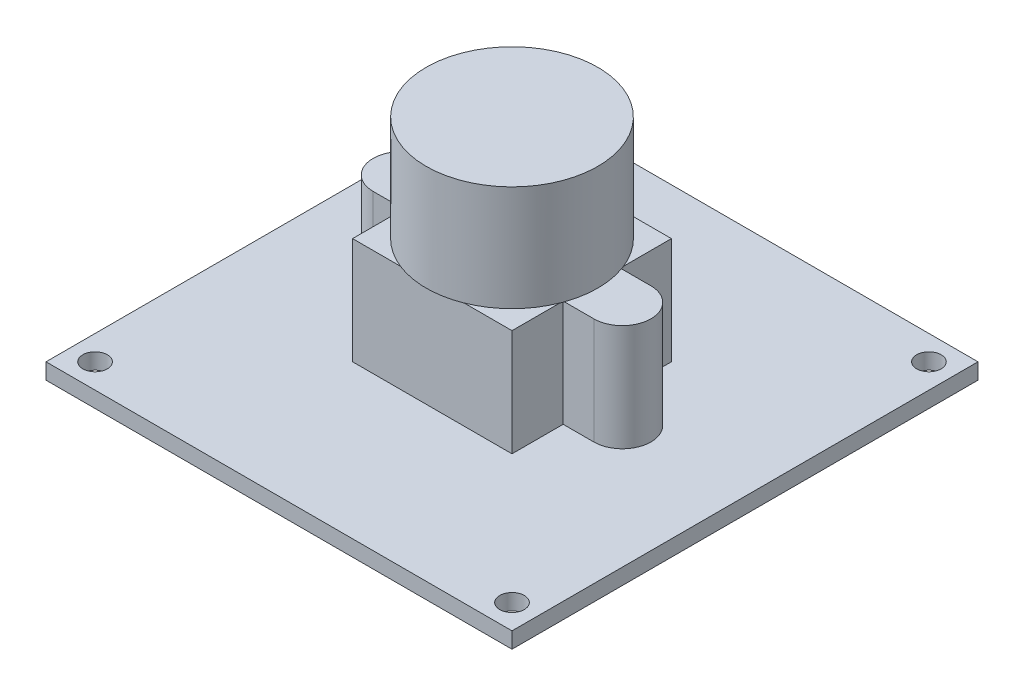
SolidWorks part; units mm, degrees
ref_plane "前视基准面" through (0, 0, 0) normal (0, 0, 1) x (1, 0, 0)
ref_plane "上视基准面" through (0, 0, 0) normal (0, 1, 0) x (1, 0, 0)
ref_plane "右视基准面" through (0, 0, 0) normal (1, 0, 0) x (0, 0, -1)
sketch "Sketch1" plane through (0, 0, 0) normal (0, 1, 0) x (1, 0, 0)
  line L0 (4.6135, 13.9942) -> (4.6135, 34.0904) construction
  line L5 (-14.3865, 13.9942) -> (23.6135, 13.9942)
  line L6 (-14.3865, 13.9942) -> (-14.3865, -24.0058)
  line L7 (-14.3865, -24.0058) -> (23.6135, -24.0058)
  line L8 (23.6135, 13.9942) -> (23.6135, -24.0058)
  line L9 (-14.3865, -5.0058) -> (-25.275, -5.0058) construction
  line L11 (-12.3865, -22.0058) -> (21.6135, -22.0058) construction
  line L12 (-12.3865, -22.0058) -> (-12.3865, 11.9942) construction
  line L13 (-12.3865, 11.9942) -> (21.6135, 11.9942) construction
  line L14 (21.6135, -22.0058) -> (21.6135, 11.9942) construction
  line L15 (-12.3865, -22.0058) -> (21.6135, 11.9942) construction
  line L16 (-12.3865, 11.9942) -> (21.6135, -22.0058) construction
  circle A0 centre (-12.3865, 11.9942) radius 1
  circle A1 centre (21.6135, 11.9942) radius 1
  circle A2 centre (21.6135, -22.0058) radius 1
  circle A3 centre (-12.3865, -22.0058) radius 1
  point P5 (4.6135, -5.0058)
  point P13 (4.6135, 13.9942)
  dimension "D1" = 38
  dimension "D2" = 38
  dimension "D3" = 34
  dimension "D4" = 34
extrude "Boss-Extrude1" add sketch "Sketch1" along normal blind 1.3
sketch "Sketch2" plane through (0, 1.3, 0) normal (0, 1, 0) x (1, 0, 0)
  line L0 (4.6135, 13.9942) -> (4.6135, -32.1036) construction
  line L2 (-14.3865, -5.0058) -> (-25.698, -5.0058) construction
  line L4 (-4.3865, -5.0058) -> (13.6135, -5.0058) construction
  line L5 (-1.8865, -11.5058) -> (11.1135, -11.5058)
  line L6 (-1.8865, -11.5058) -> (-1.8865, -7.3337)
  line L7 (-1.8865, 1.4942) -> (11.1135, 1.4942)
  line L8 (11.1135, -11.5058) -> (11.1135, -7.3337)
  line L9 (-1.8865, -11.5058) -> (11.1135, 1.4942) construction
  line L10 (-1.8865, 1.4942) -> (11.1135, -11.5058) construction
  line L11 (-4.3865, -2.6778) -> (-1.8865, -2.6778)
  line L12 (-4.3865, -7.3337) -> (-1.8865, -7.3337)
  line L13 (11.1135, -2.6778) -> (11.1135, 1.4942)
  line L14 (-1.8865, -2.6778) -> (-1.8865, 1.4942)
  line L15 (11.1135, -2.6778) -> (13.6135, -2.6778)
  line L16 (11.1135, -7.3337) -> (13.6135, -7.3337)
  arc A0 (-4.3865, -2.6778) -> (-4.3865, -7.3337) centre (-4.3865, -5.0058) ccw
  arc A1 (13.6135, -7.3337) -> (13.6135, -2.6778) centre (13.6135, -5.0058) ccw
  point P1 (4.6135, -5.0058)
  point P9 (4.6135, -5.0058)
  dimension "D1" = 13
  dimension "D2" = 13
  dimension "D3" = 18
extrude "Boss-Extrude2" add sketch "Sketch2" along normal blind 8.7
sketch "Sketch3" plane through (0, 10, 0) normal (0, 1, 0) x (1, 0, 0)
  circle A0 centre (4.6135, -5.0058) radius 7
extrude "Boss-Extrude3" add sketch "Sketch3" along normal blind 8.6
ref_axis "基准轴1" through (4.6135, 18.6, 5.0058) along (0, -1, 0)
sketch "Sketch4" plane through (0, 18.6, 0) normal (0, 1, 0) x (1, 0, 0)
  line L1 (-4.9865, -10.4058) -> (14.2135, -10.4058)
  line L2 (-4.9865, -10.4058) -> (-4.9865, 0.3942)
  line L3 (-4.9865, 0.3942) -> (14.2135, 0.3942)
  line L4 (14.2135, -10.4058) -> (14.2135, 0.3942)
  line L5 (-4.9865, -10.4058) -> (14.2135, 0.3942) construction
  line L6 (-4.9865, 0.3942) -> (14.2135, -10.4058) construction
  point P0 (4.6135, -5.0058)
  dimension "D1" = 10.8
  dimension "D2" = 19.2
ref_plane "Plane1" through (0, 518.6, 0) normal (0, 1, 0) x (1, 0, 0)
sketch "Sketch5" plane through (0, 518.6, 0) normal (0, 1, 0) x (1, 0, 0)
  line L1 (-929.7493, 520.4942) -> (938.9762, 520.4942)
  line L2 (-929.7493, 520.4942) -> (-929.7493, -530.5058)
  line L3 (-929.7493, -530.5058) -> (938.9762, -530.5058)
  line L4 (938.9762, 520.4942) -> (938.9762, -530.5058)
  line L5 (-929.7493, 520.4942) -> (938.9762, -530.5058) construction
  line L6 (-929.7493, -530.5058) -> (938.9762, 520.4942) construction
  point P0 (4.6135, -5.0058)
  dimension "D1" = 1072
  dimension "D2" = 1051
loft "Loft1" [suppressed] add profiles "Sketch5", "Sketch4"
